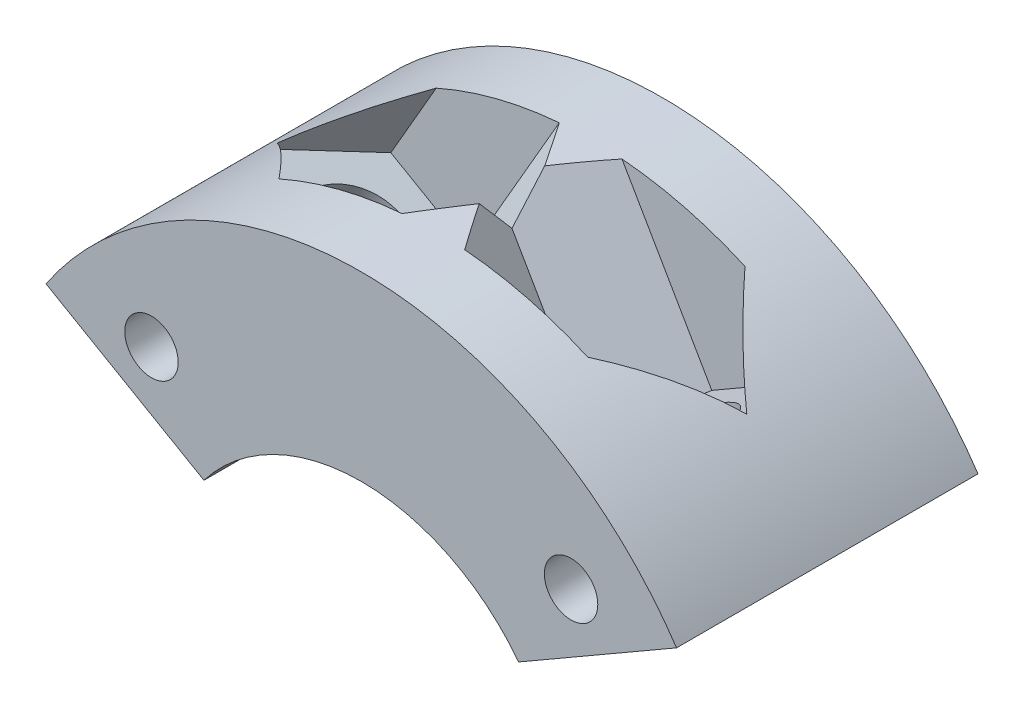
SolidWorks part; units mm, degrees
ref_plane "Front Plane" through (0, 0, 0) normal (0, 0, 1) x (1, 0, 0)
ref_plane "Top Plane" through (0, 0, 0) normal (0, 1, 0) x (1, 0, 0)
ref_plane "Right Plane" through (0, 0, 0) normal (1, 0, 0) x (0, 0, -1)
sketch "Sketch4" plane through (0, 0, 0) normal (0, 0, 1) x (1, 0, 0)
  circle A0 centre (0, 0) radius 12.7 construction
  circle A1 centre (0, 0) radius 23.7 construction
  dimension "D1" = 25.4
  dimension "D2" = 47.4
sketch "Sketch1" plane through (0, 0, 0) normal (0, 0, 1) x (1, 0, 0)
  line L0 (-26.5668, 17.8383) -> (0, 2.5) construction
  line L1 (0, 2.5) -> (26.5668, 17.8383) construction
  line L2 (0, 0) -> (0, 32) construction
  line L3 (13.258, 10.1545) -> (26.5668, 17.8383)
  line L4 (-26.5668, 17.8383) -> (-13.258, 10.1545)
  line L5 (17.6777, 17.6777) -> (0, 0) construction
  line L6 (0, 0) -> (-17.6777, 17.6777) construction
  arc A0 (-13.258, 10.1545) -> (13.258, 10.1545) centre (0, 0) cw
  arc A1 (-26.5668, 17.8383) -> (26.5668, 17.8383) centre (0, 0) cw
  circle A2 centre (-17.6777, 17.6777) radius 2.25
  circle A3 centre (17.6777, 17.6777) radius 2.25
  circle A4 centre (0, 0) radius 23.7 construction
  point P11 (27.5824, 16.2237)
  dimension "D1" = 60
  dimension "D2" = 60
  dimension "D8" = 4.5
  dimension "D3" = 32
  dimension "D4" = 7
  dimension "D5" = 45
  dimension "D6" = 45
  dimension "D7" = 25
  dimension "D9" = 2.5
extrude "Boss-Extrude1" add sketch "Sketch1" along normal mid plane 25.4 contours A2 | A1 L4 A0 L3 A3 A2 | A3 region at (0, 21.6948, 0) region at (-17.6777, 17.6777, 0) region at (17.6777, 17.6777, 0)
sketch "Sketch3" plane through (-1.0825, 1.875, 0) normal (0.5, -0.866, 0) x (0.866, 0.5, 0)
  line L0 (16.5591, 12.7) -> (16.5591, -12.7) construction
  line L2 (18.2341, -6.625) -> (25.884, -6.625)
  line L3 (25.884, -6.625) -> (29.709, 0)
  line L4 (29.709, 0) -> (25.884, 6.625)
  line L5 (25.884, 6.625) -> (18.2341, 6.625)
  line L6 (18.2341, 6.625) -> (14.4092, 0)
  line L7 (14.4092, 0) -> (18.2341, -6.625)
  line L8 (14.4092, 0) -> (29.709, 0) construction
  line L9 (18.2341, 6.625) -> (25.884, -6.625) construction
  line L10 (18.2341, -6.625) -> (25.884, 6.625) construction
  line L11 (23.7, 0) -> (-23.7, 0) construction
  circle A0 centre (22.0591, 0) radius 4.35
  point P2 (22.0591, 0)
  dimension "D1" = 8.7
  dimension "D2" = 13.25
  dimension "D3" = 5.5
extrude "Cut-Extrude1" cut sketch "Sketch3" against normal through all both and the other way through all contours A0 region at (18.0212, 12.9045, 0)
extrude "Cut-Extrude2" cut sketch "Sketch1<3>" against normal blind 8 from surface contours A3 region at (17.6777, 17.6777, 0) starting at face at (0, 19.1732, 12.7)
sketch "Sketch1<3>" plane through (0, 0, 0) normal (0, 0, 1) x (1, 0, 0) same geometry as "Sketch1"
extrude "Cut-Extrude4" cut sketch "Sketch1<5>" along normal blind 8 from surface contours A3 region at (17.6777, 17.6777, 0) starting at face at (0, 19.1732, -12.7)
sketch "Sketch1<5>" plane through (0, 0, 0) normal (0, 0, 1) x (1, 0, 0) same geometry as "Sketch1"
extrude "Cut-Extrude3" cut sketch "Sketch3<3>" against normal through all from offset 9 offset against normal yes
sketch "Sketch3<3>" plane through (-1.0825, 1.875, 0) normal (0.5, -0.866, 0) x (0.866, 0.5, 0) same geometry as "Sketch3"
mirror "Mirror1" about plane through (0, 0, 0) normal (1, 0, 0) of "Cut-Extrude1", "Cut-Extrude4", "Cut-Extrude2", "Cut-Extrude3"
sketch "Sketch5" plane through (-1.0825, 1.875, 0) normal (0.5, -0.866, 0) x (0.866, 0.5, 0)
  circle A0 centre (22.0591, 0) radius 11
  dimension "D1" = 22
extrude "Boss-Extrude2" [suppressed] add sketch "Sketch5" along normal blind 7 from offset 1
